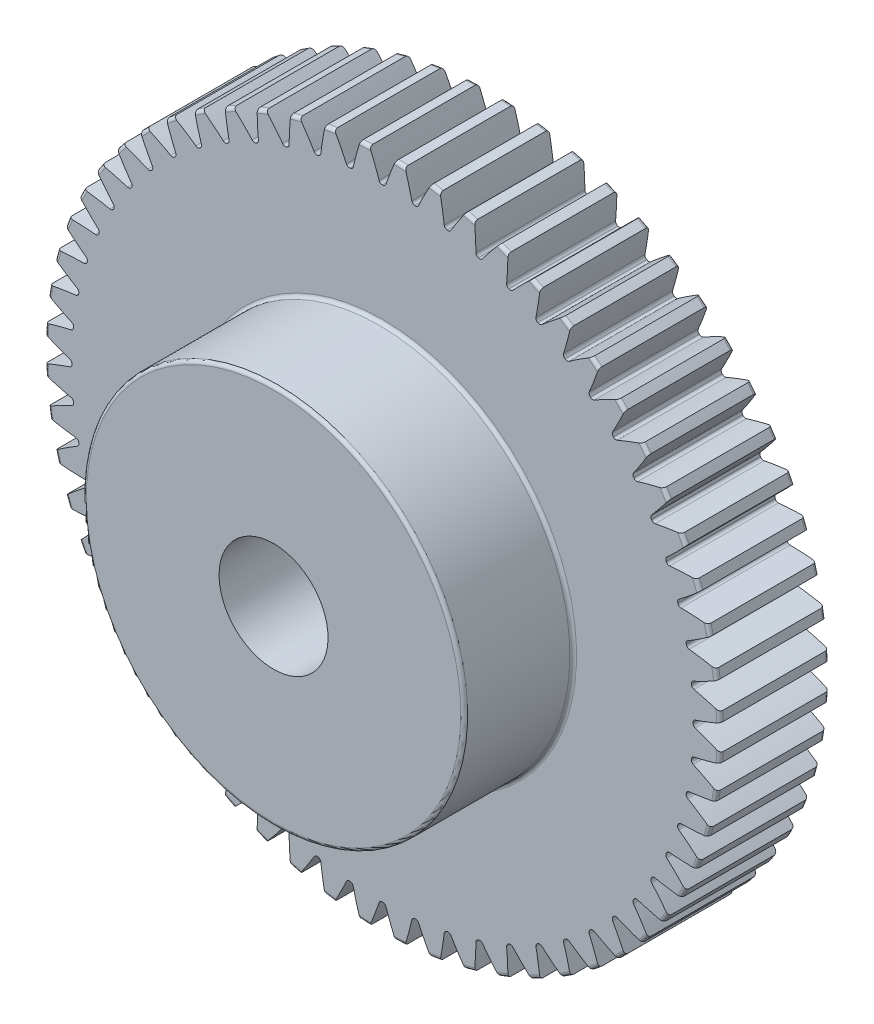
SolidWorks part; units mm, degrees
ref_plane "Front Plane" through (0, 0, 0) normal (0, 0, 1) x (1, 0, 0)
ref_plane "Top Plane" through (0, 0, 0) normal (0, 1, 0) x (1, 0, 0)
ref_plane "Right Plane" through (0, 0, 0) normal (1, 0, 0) x (0, 0, -1)
sketch "Sketch1" plane through (0, 0, 0) normal (0, 0, 1) x (1, 0, 0)
  line L0 (-762, 0) -> (762, 0) construction
  circle A0 centre (0, 0) radius 31 construction
  circle A1 centre (0, 0) radius 30 construction
  circle A2 centre (0, 0) radius 28.5 construction
  circle A3 centre (0, 0) radius 17.5 construction
  circle A4 centre (0, 0) radius 5 construction
  dimension "D2" = 1
  dimension "D3" = 2.5
  dimension "D1" = 2.5
sketch "Sketch2" plane through (0, 0, 0) normal (1, 0, 0) x (0, 0, -1)
  line L0 (0, 0) -> (-10, 0) construction
  line L1 (-10, 0) -> (-20, 0) construction
  dimension "Overall Width" = 20
  dimension "Face Width" = 10
sketch "Sketch4" plane through (0, 0, 0) normal (1, 0, 0) x (0, 0, -1)
  line L0 (-20, 5) -> (-20, 17.5)
  line L1 (-20, 17.5) -> (-10, 17.5)
  line L2 (-10, 17.5) -> (-10, 31)
  line L3 (-10, 31) -> (0, 31)
  line L4 (0, 31) -> (0, 5)
  line L5 (-10, 17.5) -> (-10, 0) construction
  line L6 (0, 31) -> (0, -31) construction
  line L7 (-10, 17.5) -> (0, 17.5) construction
  line L12 (-20, 5) -> (0, 5)
revolve "Revolve1" add sketch "Sketch4" angle 360 about L1
fillet "Fillet2" radius 0.31 4 edges at (0, 17.5, 20) (0, 17.5, 10) (0, 31, 10) (0, 31, 0)
sketch "Sketch7" plane through (0, 0, 10) normal (0, 0, 1) x (1, 0, 0)
  line L0 (0, 0) -> (0, 31) construction
  line L1 (0.7853, 29.9897) -> (1.1745, 30.9777) construction
  line L3 (1.6224, 30.9575) -> (1.5701, 29.9589) construction
  line L4 (1.5701, 29.9589) -> (1.4916, 28.4609) construction
  line L5 (0, 0) -> (1.4916, 28.4609) construction
  line L6 (0.7853, 29.9897) -> (0, 0) construction
  line L7 (0.7853, 29.9897) -> (0.8115, 30.9894) construction
  line L8 (0.7853, 29.9897) -> (0, 0) construction
  circle A0 centre (0, 0) radius 31 construction
  arc A1 (-0.0279, 28.5) -> (0.0279, 28.5) centre (0, 0) cw
  circle A2 centre (0, 0) radius 28.5 construction
  arc A3 (-0.7853, 29.9897) -> (0.7853, 29.9897) centre (0, 0) cw construction
  circle A4 centre (0, 0) radius 30 construction
  arc A5 (2.0499, 30.9322) -> (1.1947, 30.977) centre (0, 0) ccw construction
  arc A6 (0.7853, 29.9897) -> (2.3538, 29.9075) centre (0, 0) cw construction
  arc A7 (-1.1947, 30.977) -> (1.1947, 30.977) centre (0, 0) cw
  arc A8 (0.3121, 28.7029) -> (1.1947, 30.977) centre (28.6978, 18.9947) cw
  arc A9 (-0.3121, 28.7029) -> (-1.1947, 30.977) centre (-28.6978, 18.9947) ccw
  arc A10 (-0.0279, 28.5) -> (-0.3121, 28.7029) centre (-0.0282, 28.8) cw
  arc A11 (0.0279, 28.5) -> (0.3121, 28.7029) centre (0.0282, 28.8) ccw
  point P26 (-0.2432, 28.499)
  point P29 (0.2432, 28.499)
  dimension "D4" = 0.3
  dimension "D5" = 30
  dimension "D3" = 20
  dimension "D1" = 3.1416
  dimension "D2" = 1.5708
extrude "Cut-Extrude2" cut sketch "Sketch7" against normal through all
pattern_circular "CirPattern1" count 60 over 360 about axis through (0, 0, 20) along (0, 0, -1) of "Cut-Extrude2"
equation "\"D1@Sketch1\"=2.5*(\"Pitch Dia.@Sketch1\"/\"Number of Teeth@Sketch1\")"
equation "\"D1@CirPattern1\"=\"Number of Teeth@Sketch1\""
equation "\"D1@Fillet2\"=\"OD@Sketch1\"*.005"
equation "\"D1@Sketch7\"=3.14159*(\"Pitch Dia.@Sketch1\"/\"Number of Teeth@Sketch1\")"
equation "\"D2@Sketch7\"=\"D1@Sketch7\"/2"
equation "\"D4@Sketch7\"=\"D1@Sketch7\"*.0955"
equation "\"D5@Sketch7\"=\"Pitch Dia.@Sketch1\"/2"
